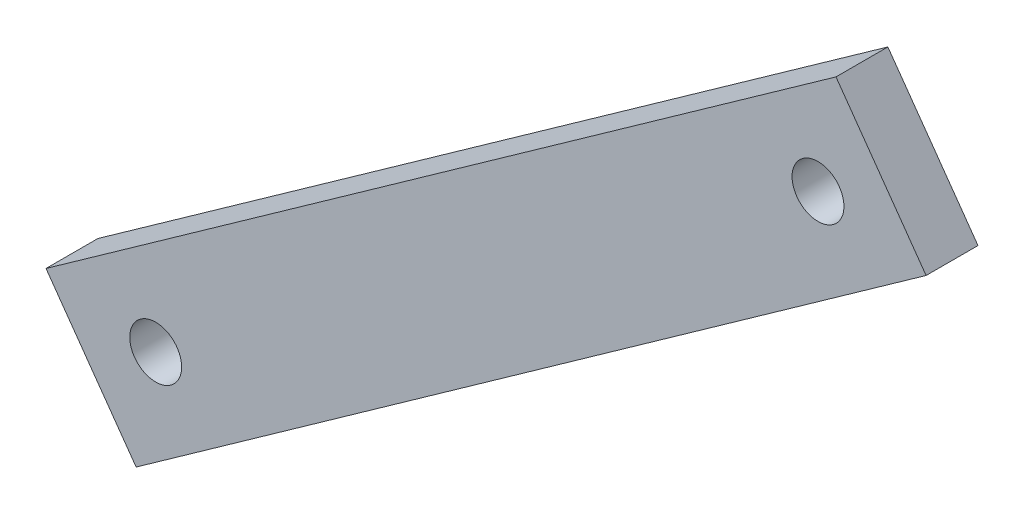
SolidWorks part; units mm, degrees
ref_plane "Front Plane" through (0, 0, 0) normal (0, 0, 1) x (1, 0, 0)
ref_plane "Top Plane" through (0, 0, 0) normal (0, 1, 0) x (1, 0, 0)
ref_plane "Right Plane" through (0, 0, 0) normal (1, 0, 0) x (0, 0, -1)
sketch "Sketch1" plane through (0, 0, 0) normal (0, 0, 1) x (1, 0, 0)
  line L0 (-67.8067, 8.4523) -> (-29.1397, 35.9059)
  line L1 (-67.8067, 8.4523) -> (-63.3953, 2.2391)
  line L2 (-63.3953, 2.2391) -> (-24.7284, 29.6926)
  line L3 (-24.7284, 29.6926) -> (-29.1397, 35.9059)
  line L4 (-67.8067, 8.4523) -> (-64.6431, 10.6985)
  line L5 (-64.6431, 10.6985) -> (-60.2317, 4.4852)
  line L6 (-65.601, 5.3457) -> (-26.934, 32.7993)
  line L7 (-29.1397, 35.9059) -> (-32.2252, 33.7152)
  line L8 (-32.2252, 33.7152) -> (-27.8139, 27.5019)
  circle A0 centre (-62.4374, 7.5919) radius 1.27
  circle A1 centre (-30.0195, 30.6086) radius 1.27
  dimension "D1" = 47.4218
extrude "Boss-Extrude1" add sketch "Sketch1" along normal blind 2.54 contours L3 L0 L1 L2
extrude "Cut-Extrude1" cut sketch "Sketch1<4>" along normal blind 3.302 contours A1 | A0
sketch "Sketch1<4>" plane through (0, 0, 0) normal (0, 0, 1) x (1, 0, 0) same geometry as "Sketch1"
